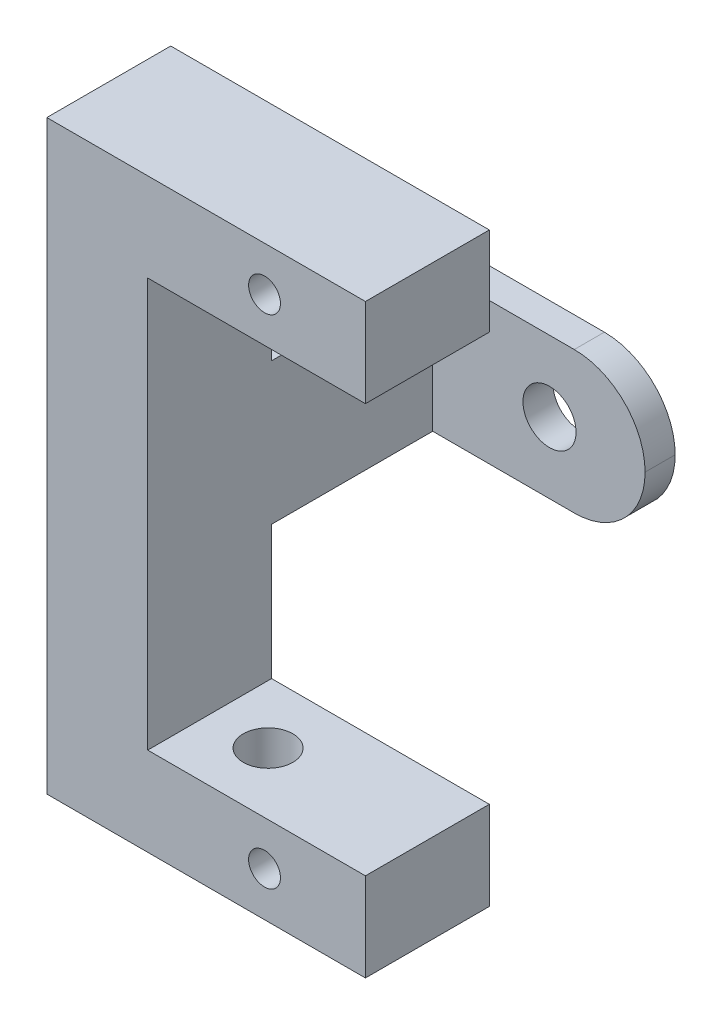
SolidWorks part; units mm, degrees
ref_plane "Front Plane" through (0, 0, 0) normal (0, 0, 1) x (1, 0, 0)
ref_plane "Top Plane" through (0, 0, 0) normal (0, 1, 0) x (1, 0, 0)
ref_plane "Right Plane" through (0, 0, 0) normal (1, 0, 0) x (0, 0, -1)
sketch "Schizzo1" plane through (0, 0, 0) normal (0, 0, 1) x (1, 0, 0)
  line L0 (8.3, 11.55) -> (-4, 11.55)
  line L5 (-4, 11.55) -> (-4, -11.55)
  line L6 (-4, -11.55) -> (8.3, -11.55)
  line L7 (8.3, -11.55) -> (8.3, -16.55)
  line L8 (8.3, -16.55) -> (-9.7, -16.55)
  line L9 (-9.7, -16.55) -> (-9.7, 16.55)
  line L10 (-9.7, 16.55) -> (8.3, 16.55)
  line L11 (8.3, 16.55) -> (8.3, 11.55)
  point P2 (-4, 0)
  dimension "D1" = 23.1
  dimension "D2" = 12.3
  dimension "D3" = 18
  dimension "D4" = 5
  dimension "D5" = 4
extrude "Estrusione-Estrusione1" add sketch "Schizzo1" along normal blind 7
sketch "Schizzo2" plane through (0, 0, 7) normal (0, 0, 1) x (1, 0, 0)
  line L0 (-4, 11.55) -> (8.3, 11.55) construction
  line L1 (0, 0) -> (14.3967, 0) construction
  line L2 (8.3, 11.55) -> (8.3, 16.55) construction
  circle A0 centre (2.6, 14.05) radius 0.9
  circle A1 centre (2.6, -14.05) radius 0.9
  dimension "D1" = 1.8
  dimension "D2" = 2.5
  dimension "D3" = 5.7
extrude "Taglio-Estrusione1" cut sketch "Schizzo2" against normal through all
sketch "Schizzo3" plane through (0, -16.55, 0) normal (0, -1, 0) x (1, 0, 0)
  line L0 (-9.7, 0) -> (8.3, 0) construction
  line L1 (-9.7, 7) -> (-9.7, 0) construction
  circle A0 centre (-0.7, 3.5) radius 1.4
  point P4 (-0.7, 0)
  point P7 (-9.7, 3.5)
  dimension "D1" = 2.8
extrude "Taglio-Estrusione2" cut sketch "Schizzo3" against normal up to next
sketch "Schizzo4" plane through (0, 0, 0) normal (0, 0, -1) x (-1, 0, 0)
  line L0 (4, -11.55) -> (4, 11.55) construction
  line L1 (4, 4) -> (9.7, 4)
  line L2 (4, 4) -> (4, -4)
  line L3 (4, -4) -> (9.7, -4)
  line L4 (9.7, 4) -> (9.7, -4)
  line L5 (9.7, 16.55) -> (9.7, -16.55) construction
  point P8 (9.7, 0)
  point P9 (9.7, 0)
  dimension "D1" = 8
extrude "Estrusione-Estrusione2" add sketch "Schizzo4" along normal blind 10.8
sketch "Schizzo5" plane through (-4, 0, 0) normal (1, 0, 0) x (0, 0, -1)
  line L0 (10.8, 4) -> (0, 4) construction
  line L1 (10.8, 4) -> (9.1, 4)
  line L2 (10.8, 4) -> (10.8, -4)
  line L3 (10.8, -4) -> (9.1, -4)
  line L4 (9.1, 4) -> (9.1, -4)
  line L5 (10.8, 4) -> (10.8, -4) construction
  line L6 (10.8, -4) -> (0, -4) construction
  dimension "D1" = 1.7
extrude "Estrusione-Estrusione3" add sketch "Schizzo5" along normal blind 12
fillet "Raccordo1" radius 4 2 edges at (8, 4, -9.95) (8, -4, -9.95)
sketch "Schizzo6" plane through (0, 0, -10.8) normal (0, 0, -1) x (-1, 0, 0)
  line L0 (-2.6, 4) -> (-2.6, -4) construction
  line L1 (9.7, 4) -> (-4, 4) construction
  line L2 (-4, -4) -> (9.7, -4) construction
  line L3 (9.7, -4) -> (9.7, 4) construction
  circle A0 centre (-2.6, 0) radius 1.5
  dimension "D1" = 3
  dimension "D2" = 12.3
extrude "Taglio-Estrusione3" cut sketch "Schizzo6" against normal up to next
